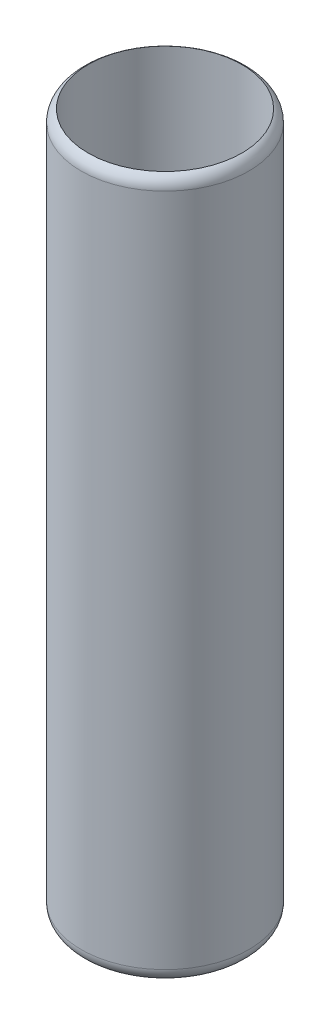
SolidWorks part; units mm, degrees
ref_plane "Alzado" through (0, 0, 0) normal (0, 0, 1) x (1, 0, 0)
ref_plane "Planta" through (0, 0, 0) normal (0, 1, 0) x (1, 0, 0)
ref_plane "Vista lateral" through (0, 0, 0) normal (1, 0, 0) x (0, 0, -1)
sketch "Sketch1" plane through (0, 0, 0) normal (0, 1, 0) x (1, 0, 0)
  circle A0 centre (0, 0) radius 6
  dimension "D1" = 12
extrude "Boss-Extrude1" add sketch "Sketch1" along normal blind 50
sketch "Sketch2" plane through (0, 50, 0) normal (0, 1, 0) x (1, 0, 0)
  circle A0 centre (0, 0) radius 5.5
  circle A1 centre (0, 0) radius 6 construction
  dimension "D1" = 0.5
extrude "Cut-Extrude1" cut sketch "Sketch2" against normal blind 50
fillet "Fillet1" radius 1 1 edges at (0, 50, 6)
fillet "Fillet2" radius 1 1 edges at (0, 0, 6)
